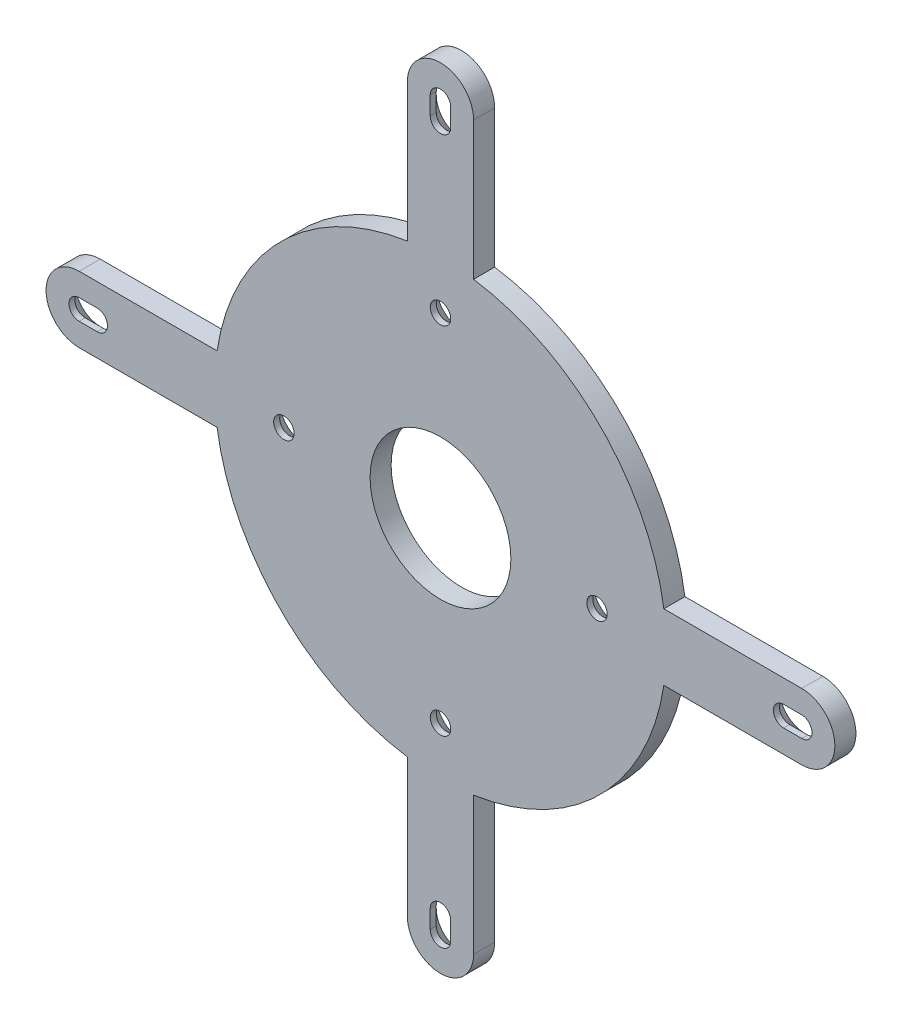
SolidWorks part; units mm, degrees
ref_plane "Front Plane" through (0, 0, 0) normal (0, 0, 1) x (1, 0, 0)
ref_plane "Top Plane" through (0, 0, 0) normal (0, 1, 0) x (1, 0, 0)
ref_plane "Right Plane" through (0, 0, 0) normal (1, 0, 0) x (0, 0, -1)
sketch "Sketch1" plane through (0, 0, 0) normal (0, 0, 1) x (1, 0, 0)
  line L0 (60, 0) -> (-60, 0) construction
  line L1 (60, -5.5) -> (-60, -5.5)
  line L2 (60, 5.5) -> (-60, 5.5)
  line L3 (0, -60) -> (0, 60) construction
  line L4 (-5.5, -60) -> (-5.5, 60)
  line L5 (5.5, -60) -> (5.5, 60)
  line L6 (-60, 0) -> (-57, 0) construction
  line L7 (-60, 1.7) -> (-57, 1.7)
  line L8 (-60, -1.7) -> (-57, -1.7)
  line L9 (0, -60) -> (0, -57) construction
  line L10 (-1.7, -60) -> (-1.7, -57)
  line L11 (1.7, -60) -> (1.7, -57)
  line L12 (60, 0) -> (57, 0) construction
  line L13 (60, -1.7) -> (57, -1.7)
  line L14 (60, 1.7) -> (57, 1.7)
  line L15 (0, 60) -> (0, 57) construction
  line L16 (1.7, 60) -> (1.7, 57)
  line L17 (-1.7, 60) -> (-1.7, 57)
  circle A0 centre (0, 0) radius 37.5
  arc A1 (60, -5.5) -> (60, 5.5) centre (60, 0) ccw
  arc A2 (-60, 5.5) -> (-60, -5.5) centre (-60, 0) ccw
  arc A3 (-5.5, -60) -> (5.5, -60) centre (0, -60) ccw
  arc A4 (5.5, 60) -> (-5.5, 60) centre (0, 60) ccw
  circle A5 centre (0, 29.5) radius 1.7
  circle A6 centre (26, 0) radius 1.7
  circle A7 centre (-26, 0) radius 1.7
  circle A8 centre (0, -29.5) radius 1.7
  arc A13 (-60, 1.7) -> (-60, -1.7) centre (-60, 0) ccw
  arc A14 (-57, -1.7) -> (-57, 1.7) centre (-57, 0) ccw
  arc A15 (-1.7, -60) -> (1.7, -60) centre (0, -60) ccw
  arc A16 (1.7, -57) -> (-1.7, -57) centre (0, -57) ccw
  arc A17 (60, -1.7) -> (60, 1.7) centre (60, 0) ccw
  arc A18 (57, 1.7) -> (57, -1.7) centre (57, 0) ccw
  arc A19 (1.7, 60) -> (-1.7, 60) centre (0, 60) ccw
  arc A20 (-1.7, 57) -> (1.7, 57) centre (0, 57) ccw
  point P5 (0, 0)
  point P11 (0, 0)
  point P31 (-58.5, 0)
  point P36 (0, -58.5)
  point P43 (58.5, 0)
  point P50 (0, 58.5)
  dimension "D1" = 75
  dimension "D3" = 3.4
  dimension "D4" = 5.5
  dimension "D5" = 1.7
  dimension "D2" = 120
  dimension "D6" = 3
extrude "Boss-Extrude1" add sketch "Sketch1" along normal blind 3.5 contours L2 A2 L1 A0 | L2 A0 L1 L4 A7 | L1 L5 L2 L4 | L5 A0 L4 L2 A5 | L5 A4 L4 A0 | L1 A0 L2 L5 A6 | L1 A1 L2 A0 | L4 A0 L5 L1 A8 | L4 A3 L5 A0 | A0 region at (50.3395, 0, 0) region at (21.3113, 0, 0) region at (0, -21.2183, 0) region at (0, 0, 0) region at (0, -50.3395, 0) region at (-21.3113, 0, 0) region at (0, 21.2183, 0) region at (0, 50.3395, 0) region at (-50.3395, 0, 0)
extrude "Cut-Extrude1" cut sketch "Sketch1<3>" along normal blind 13 contours A7 | A5 | A8 | A6
sketch "Sketch1<3>" plane through (0, 0, 0) normal (0, 0, 1) x (1, 0, 0) same geometry as "Sketch1"
chamfer "Chamfer1" distance 2.5 angle 45 20 edges at (0, 55.3, 0) (1.7, 58.5, 0) (-1.7, 58.5, 0) (0, 61.7, 0) (-58.5, -1.7, 0) (-61.7, 0, 0) (-55.3, 0, 0) (-58.5, 1.7, 0) (0, -61.7, 0) (1.7, -58.5, 0) (-1.7, -58.5, 0) (0, -55.3, 0) (58.5, -1.7, 0) (61.7, 0, 0) (55.3, 0, 0) (58.5, 1.7, 0) (27.7, 0, 0) (1.7, 29.5, 0) (1.7, -29.5, 0) (-24.3, 0, 0)
sketch "Sketch2" plane through (0, 0, 0) normal (0, 0, -1) x (-1, 0, 0)
  circle A0 centre (0, 0) radius 11.6921
extrude "Cut-Extrude2" cut sketch "Sketch2" against normal blind 10
